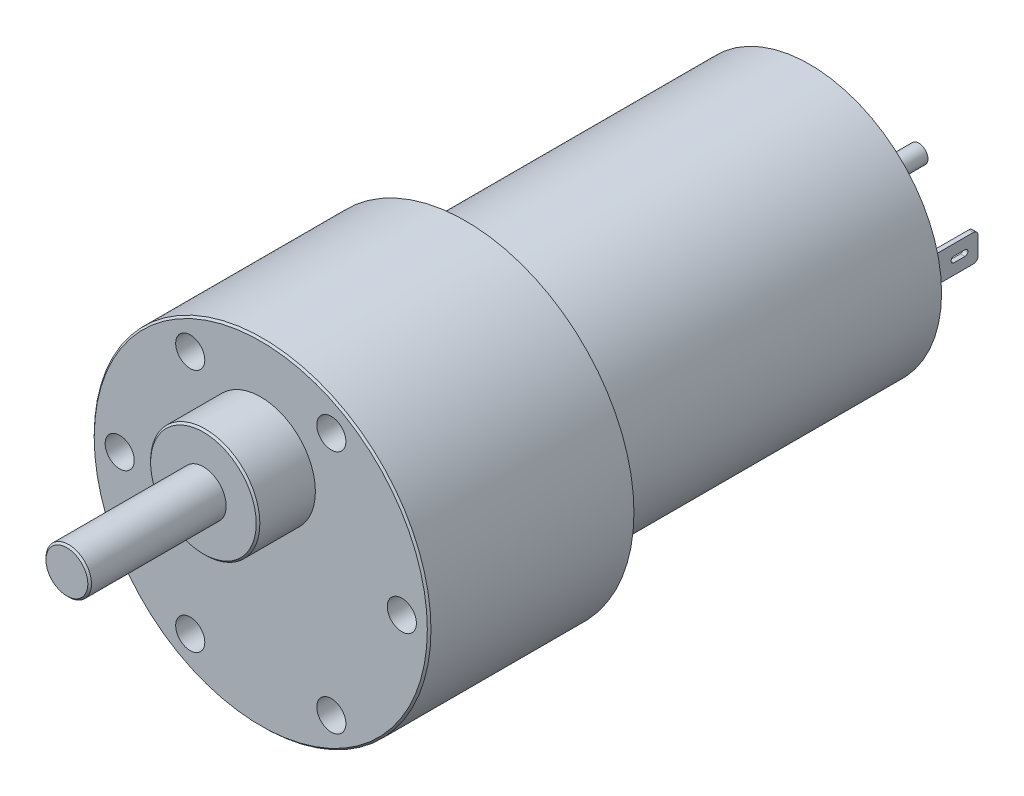
SolidWorks part; units mm, degrees
ref_plane "Front Plane" through (0, 0, 0) normal (0, 0, 1) x (1, 0, 0)
ref_plane "Top Plane" through (0, 0, 0) normal (0, 1, 0) x (1, 0, 0)
ref_plane "Right Plane" through (0, 0, 0) normal (1, 0, 0) x (0, 0, -1)
sketch "Sketch1" plane through (0, 0, 0) normal (0, 0, 1) x (1, 0, 0)
  circle A0 centre (0, 0) radius 18.5
  dimension "D1" = 37
extrude "Boss-Extrude1" add sketch "Sketch1" along normal blind 22.5
sketch "Sketch2" plane through (0, 0, 22.5) normal (0, 0, 1) x (1, 0, 0)
  line L0 (-18.5, 0) -> (18.5, 0) construction
  line L1 (0, 18.5) -> (0, -18.5) construction
  line L2 (11.1332, 19.2832) -> (-10.7359, -18.5952) construction
  line L3 (-11.3747, 19.7016) -> (11.6905, -20.2486) construction
  circle A0 centre (0, 0) radius 18.5 construction
  circle A1 centre (0, 0) radius 15.5 construction
  circle A2 centre (-7.75, 13.4234) radius 1.6
  circle A3 centre (7.75, 13.4234) radius 1.6
  circle A4 centre (-15.5, 0) radius 1.6
  circle A5 centre (-7.75, -13.4234) radius 1.6
  circle A6 centre (7.75, -13.4234) radius 1.6
  circle A7 centre (15.5, 0) radius 1.6
  dimension "D3" = 31
  dimension "D4" = 3.2
  dimension "D1" = 120
  dimension "D2" = 120
extrude "Cut-Extrude1" cut sketch "Sketch2" against normal blind 3.5
sketch "Sketch3" plane through (0, 0, 22.5) normal (0, 0, 1) x (1, 0, 0)
  line L0 (0, 0) -> (0, 18.5) construction
  circle A0 centre (0, 0) radius 18.5 construction
  circle A1 centre (0, 7) radius 6
  circle A2 centre (0, 7) radius 2.5
  dimension "D1" = 12
  dimension "D3" = 5
  dimension "D2" = 7
extrude "Boss-Extrude2" add sketch "Sketch3" along normal blind 21.3 contours A2 L0 | L0 A2 region at (-1.061, 7, 22.5) region at (1.061, 7, 22.5)
extrude "Boss-Extrude3" add sketch "Sketch3<3>" along normal blind 6.3 contours A1 L0 A2 | L0 A1 A2 region at (-2.8585, 7, 22.5) region at (2.8585, 7, 22.5)
sketch "Sketch3<3>" plane through (0, 0, 22.5) normal (0, 0, 1) x (1, 0, 0) same geometry as "Sketch3"
sketch "Sketch4" plane through (0, 0, 0) normal (0, 0, -1) x (-1, 0, 0)
  circle A0 centre (0, 0) radius 14.5
  dimension "D1" = 29
extrude "Boss-Extrude4" add sketch "Sketch4" along normal blind 37.8
sketch "Sketch5" plane through (0, 0, -37.8) normal (0, 0, -1) x (-1, 0, 0)
  line L0 (-14.5, 0) -> (14.5, 0) construction
  circle A0 centre (0, 0) radius 5
  circle A1 centre (0, 0) radius 14.5 construction
  dimension "D1" = 10
extrude "Boss-Extrude5" add sketch "Sketch5" along normal blind 3
sketch "Sketch6" plane through (0, 0, -40.8) normal (0, 0, -1) x (-1, 0, 0)
  circle A0 centre (0, 0) radius 1
  dimension "D1" = 2
extrude "Boss-Extrude6" add sketch "Sketch6" along normal blind 9
sketch "Sketch7" plane through (0, 0, -37.8) normal (0, 0, -1) x (-1, 0, 0)
  line L0 (-14.5, 0) -> (14.5, 0) construction
  line L1 (0, 0) -> (0, -10.7163) construction
  line L2 (-12, 1.5) -> (-11.5, 1.5)
  line L3 (-12, 1.5) -> (-12, -1.5)
  line L4 (-12, -1.5) -> (-11.5, -1.5)
  line L5 (-11.5, 1.5) -> (-11.5, -1.5)
  line L6 (12, 1.5) -> (11.5, 1.5)
  line L7 (12, -1.5) -> (11.5, -1.5)
  line L8 (12, 1.5) -> (12, -1.5)
  line L9 (11.5, 1.5) -> (11.5, -1.5)
  circle A0 centre (0, 0) radius 14.5 construction
  circle A1 centre (0, 0) radius 14.5 construction
  dimension "D1" = 3
  dimension "D2" = 1.5
  dimension "D3" = 0.5
  dimension "D4" = 11.5
extrude "Boss-Extrude7" add sketch "Sketch7" along normal blind 6.5
sketch "Sketch8" plane through (12, 0, 0) normal (1, 0, 0) x (0, 0, -1)
  line L0 (42.8651, 0) -> (41.6651, 0) construction
  line L1 (42.8651, -0.3201) -> (41.6651, -0.3201)
  line L2 (42.8651, 0.3201) -> (41.6651, 0.3201)
  line L3 (42.8651, 0) -> (44.3, 0) construction
  line L4 (44.3, 1.5) -> (44.3, -1.5) construction
  arc A0 (42.8651, -0.3201) -> (42.8651, 0.3201) centre (42.8651, 0) ccw
  arc A1 (41.6651, 0.3201) -> (41.6651, -0.3201) centre (41.6651, 0) ccw
  point P2 (42.2651, 0)
  dimension "D1" = 1.2
extrude "Cut-Extrude2" cut sketch "Sketch8" against normal blind 0.5
mirror "Mirror2" about plane through (0, 0, 0) normal (1, 0, 0) of "Cut-Extrude2"
fillet "Fillet1" radius 0.5 4 edges at (-11.75, 1.5, -44.3) (-11.75, -1.5, -44.3) (11.75, 1.5, -44.3) (11.75, -1.5, -44.3)
chamfer "Chamfer1" distance 0.2 angle 45 3 edges at (18.5, 0, 22.5) (6, 7, 28.8) (2.5, 7, 43.8)
ref_plane "Plane1" through (0, 7, 0) normal (0, 1, 0) x (1, 0, 0)
